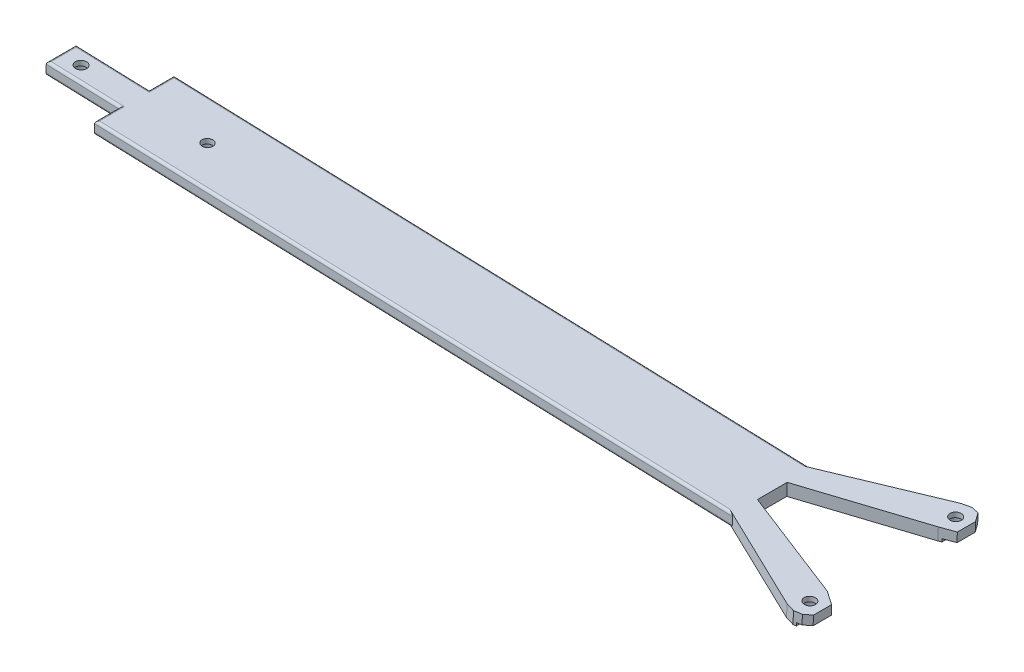
SolidWorks part; units mm, degrees
ref_plane "Front Plane" through (0, 0, 0) normal (0, 0, 1) x (1, 0, 0)
ref_plane "Top Plane" through (0, 0, 0) normal (0, 1, 0) x (1, 0, 0)
ref_plane "Right Plane" through (0, 0, 0) normal (1, 0, 0) x (0, 0, -1)
sketch "Sketch1" plane through (0.1422, 4.2506, 0) normal (-0.0334, -0.9994, 0) x (0.9994, -0.0334, 0)
  line L1 (16.1397, 116.2) -> (18.8636, 118.021)
  line L2 (-6.1364, 113) -> (14.3358, 122.5)
  line L3 (17.6397, 122.7) -> (18.8636, 121.6881)
  line L4 (-149.5566, 108) -> (-134.8067, 108)
  line L5 (-149.5566, 102) -> (-134.8067, 102)
  line L6 (-149.5566, 102) -> (-149.5566, 108)
  line L7 (-134.8067, 99.6499) -> (-134.8067, 110.3499) construction
  line L8 (-134.8067, 108) -> (-134.8067, 113)
  line L9 (-134.8067, 113) -> (-6.1364, 113)
  line L10 (-134.8067, 102) -> (-134.8067, 97)
  line L11 (-134.8067, 97) -> (-6.1364, 97)
  line L15 (18.8636, 89.021) -> (18.8636, 92.6881) construction
  line L19 (18.8636, 118.021) -> (18.8636, 121.6881) construction
  line L20 (16.1397, 87) -> (14.3397, 87.5)
  line L21 (17.6397, 87.3) -> (16.1397, 87)
  line L22 (16.1397, 93.8) -> (18.8636, 92.6881)
  line L23 (18.8636, 89.021) -> (18.8636, 92.6881)
  line L25 (14.3358, 122.5) -> (16.1397, 123)
  line L26 (16.1397, 123) -> (17.6397, 122.7)
  line L27 (18.8636, 118.021) -> (18.8636, 121.6881)
  line L29 (16.1397, 116.2) -> (-6.1364, 108)
  line L31 (18.8636, 89.021) -> (17.6397, 87.3)
  line L32 (14.3397, 87.5) -> (-6.1364, 97)
  line L33 (16.1397, 93.8) -> (-6.1364, 102)
  line L34 (-6.1364, 108) -> (-6.1364, 102)
  circle A0 centre (16.1397, 119.7) radius 1.15 construction
  circle A1 centre (16.1397, 90.3) radius 1.15 construction
  circle A2 centre (-145.5566, 105) radius 1.15 construction
  circle A3 centre (-120.0566, 105) radius 1.1 construction
  circle A4 centre (16.1397, 119.7) radius 1.15
  circle A5 centre (16.1397, 90.3) radius 1.15
  circle A6 centre (-145.5566, 105) radius 1.15
  circle A7 centre (-120.0566, 105) radius 1.1
  point P0 (18.8636, 119.8546)
  point P1 (16.2687, 87.667)
  point P24 (16.1397, 86.8658)
  point P27 (0, 0)
  point P28 (14.3358, 86.6044)
  point P29 (16.1397, 87.691)
  point P30 (0, 0)
  point P34 (16.1397, 87.691)
  point P36 (0, 0)
  point P39 (0, 0)
  point P43 (17.6397, 87.5)
  point P47 (16.2687, 87)
  point P48 (0, 0)
  point P49 (17.6397, 87.5)
  dimension "D1" = 3
  dimension "D2" = 3
  dimension "D3" = 16
  dimension "D4" = 8
  dimension "D5" = 25
  dimension "D6" = 4
  dimension "D7" = 1.8039
  dimension "D8" = 3.5
  dimension "D9" = 6
  dimension "D10" = 2.8
  dimension "D11" = 0.5
  dimension "D12" = 1.5
  dimension "D13" = 3
  dimension "D14" = 3.5
  dimension "D15" = 1.8
  dimension "D16" = 2.8
  dimension "D17" = 0.5
  dimension "D18" = 1.5
  dimension "D19" = 5
  dimension "D20" = 3
extrude "Boss-Extrude1" add sketch "Sketch1" along normal blind 2.5
sketch "Sketch2" plane through (0.0586, 1.752, 0) normal (-0.0334, -0.9994, 0) x (0.9994, -0.0334, 0)
  circle A0 centre (-145.5349, 104.9216) radius 2.1
  circle A1 centre (-120.0566, 105) radius 2.1
  circle A2 centre (16.1397, 119.7) radius 2.1
  circle A3 centre (16.1397, 90.3) radius 2.1
  dimension "D1" = 4.2
extrude "Cut-Extrude1" cut sketch "Sketch2" against normal blind 1.5
sketch "Sketch3" plane through (0.0586, 1.752, 0) normal (-0.0334, -0.9994, 0) x (0.9994, -0.0334, 0)
  line L0 (-6.1364, 113) -> (-134.8067, 113) construction
  line L1 (-113.8345, 108) -> (-18.3297, 108)
  line L2 (-113.8345, 108) -> (-113.8345, 102)
  line L3 (-113.8345, 102) -> (-18.3297, 102)
  line L4 (-18.3297, 108) -> (-18.3297, 102)
  line L5 (-134.8067, 97) -> (-6.1364, 97) construction
  dimension "D1" = 5
  dimension "D2" = 5
extrude "Boss-Extrude2" add sketch "Sketch3" along normal blind 1.5
fillet "Fillet1" radius 0.5 8 edges at (-65.9866, 3.9616, 108) (-113.7122, 5.5583, 105) (-18.2609, 2.3649, 105) (-65.9866, 3.9616, 102) (-18.311, 0.8657, 105) (-66.0367, 2.4625, 108) (-113.7624, 4.0592, 105) (-66.0367, 2.4625, 102)
fillet "Fillet2" radius 0.5 14 edges at (-141.9599, 9.0048, 102) (-149.3307, 9.2514, 105) (-141.9599, 9.0048, 108) (-134.5891, 8.7582, 110.5) (-134.5891, 8.7582, 99.5) (-70.2899, 6.607, 113) (-70.2899, 6.607, 97) (-134.6727, 6.2596, 99.5) (-70.3735, 4.1084, 97) (-70.3735, 4.1084, 113) (-134.6727, 6.2596, 110.5) (-142.0435, 6.5062, 108) (-149.4143, 6.7528, 105) (-142.0435, 6.5062, 102)
sketch "Sketch4" plane through (0.0586, 1.752, 0) normal (-0.0334, -0.9994, 0) x (0.9994, -0.0334, 0)
  line L0 (18.8636, 118.021) -> (18.8636, 121.6881) construction
  line L1 (18.8636, 89.021) -> (18.8636, 92.6881) construction
  line L2 (18.8636, 118.021) -> (18.8636, 121.6881)
  line L3 (18.8636, 89.021) -> (18.8636, 92.6881)
  line L5 (16.7035, 123.9672) -> (18.8636, 123.9672)
  line L6 (16.7035, 123.9672) -> (16.7035, 85.5707)
  line L7 (16.7035, 85.5707) -> (18.8636, 85.5707)
  line L8 (18.8636, 123.9672) -> (18.8636, 85.5707)
  circle M11 centre (16.1397, 119.7) radius 2.1
  circle M12 centre (16.1397, 90.3) radius 2.1
  line M16 (16.1397, 87) -> (17.6397, 87.3)
  line M17 (17.6397, 87.3) -> (18.8636, 89.021)
  line M18 (18.8636, 89.021) -> (18.8636, 92.6881)
  line M19 (18.8636, 92.6881) -> (16.1397, 93.8)
  line M23 (16.1397, 116.2) -> (18.8636, 118.021)
  line M24 (18.8636, 118.021) -> (18.8636, 121.6881)
  line M25 (18.8636, 121.6881) -> (17.6397, 122.7)
  line M26 (17.6397, 122.7) -> (16.1397, 123)
extrude "Cut-Extrude2" cut sketch "Sketch4" against normal blind 0.6 contours L6 M19 M12 M16 M17 M18 | L6 M26 M11 M23 M24 M25 region at (17.7952, 1.1586, 117.3544) region at (18.8436, 1.1235, 90.8546)
